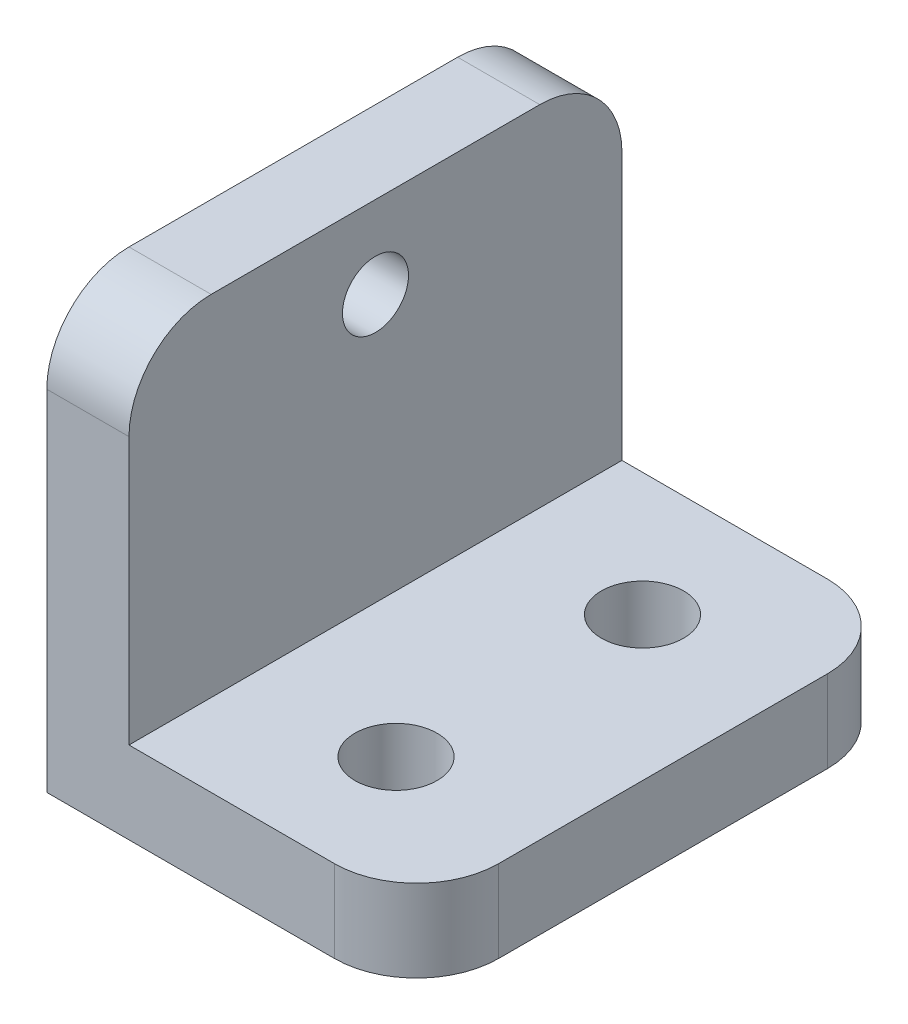
SolidWorks part; units mm, degrees
material "6061-T6 (SS)"
ref_plane "Front Plane" through (0, 0, 0) normal (0, 0, 1) x (1, 0, 0)
ref_plane "Top Plane" through (0, 0, 0) normal (0, 1, 0) x (1, 0, 0)
ref_plane "Right Plane" through (0, 0, 0) normal (1, 0, 0) x (0, 0, -1)
sketch "Sketch8" plane through (0, 0, 0) normal (0, 1, 0) x (1, 0, 0)
  line L0 (0, 19.05) -> (0, -19.05) construction
  line L1 (-14.2875, -19.05) -> (14.2875, -19.05)
  line L2 (-14.2875, -19.05) -> (-14.2875, 19.05)
  line L3 (-14.2875, 19.05) -> (14.2875, 19.05)
  line L4 (14.2875, -19.05) -> (14.2875, 19.05)
  line L5 (-14.2875, -19.05) -> (14.2875, 19.05) construction
  line L6 (-14.2875, 19.05) -> (14.2875, -19.05) construction
  line L7 (-7.9375, 19.05) -> (-7.9375, -19.05)
  point P0 (0, 0)
  dimension "D1" = 28.575
  dimension "D2" = 38.1
  dimension "D3" = 6.35
extrude "Boss-Extrude2" add sketch "Sketch8" along normal blind 6.35 contours L7 L3 L2 L1 | L3 L7 L1 L4 region at (-11.1125, 0, 0) region at (3.175, 0, 0)
extrude "Boss-Extrude3" add sketch "Sketch8<3>" along normal blind 26.9875 from surface contours L7 L3 L2 L1 region at (-11.1125, 0, 0) starting at face at (0, 6.35, 0)
sketch "Sketch8<3>" plane through (0, 0, 0) normal (0, 1, 0) x (1, 0, 0) same geometry as "Sketch8"
sketch "Sketch9" plane through (0, 0, 0) normal (0, 1, 0) x (1, 0, 0)
  line L1 (14.2875, 19.05) -> (-7.9375, 19.05) construction
  line L2 (14.2875, 19.05) -> (14.2875, -19.05) construction
  line L3 (14.2875, -19.05) -> (-7.9375, -19.05) construction
  line L4 (-7.9375, 19.05) -> (-7.9375, -19.05) construction
  line L6 (3.175, 19.05) -> (3.175, 0) construction
  line L7 (-7.9375, 0) -> (3.175, 0) construction
  line L8 (-7.9375, 0) -> (3.175, 19.05) construction
  line L9 (-7.9375, 19.05) -> (3.175, 0) construction
  line L10 (-14.2875, 19.05) -> (-7.9375, 0) construction
  line L11 (-7.9375, 19.05) -> (-14.2875, 0) construction
  line L12 (-7.9375, 19.05) -> (-7.9375, -19.05) construction
  point P4 (3.175, 9.525)
  point P5 (3.175, -9.525)
  point P10 (-2.3812, 9.525)
  point P14 (8.7313, 9.525)
  point P15 (8.7312, 0)
  point P16 (-2.3812, -9.525)
  point P17 (8.7313, -9.525)
  point P18 (-2.3812, 0)
  point P20 (-11.1125, 9.525)
  point P24 (-11.1125, -9.525)
hole_wizard "1/4 (0.25) Diameter Hole2" positions "Sketch10" profile "Sketch11" hole size "1/4" standard "ANSI Inch" end condition through all
sketch "Sketch10" plane through (0, 6.35, 0) normal (0, 1, 0) x (1, 0, 0)
  point P34 (3.175, -9.525)
  point P37 (3.175, 9.525)
sketch "Sketch11" plane through (3.175, 6.35, 9.525) normal (1, 0, 0) x (0, 0, 1)
  line L0 (0, 0) -> (0, 6.35)
  line L1 (0, 6.35) -> (3.175, 6.35)
  line L2 (3.175, 6.35) -> (3.175, 0)
  line L5 (3.175, 0) -> (0, 0)
  line L11 (0, -6.35) -> (0, 107.95) construction
  dimension "Thru Hole Dia." = 6.35
  dimension "Thru Hole Depth" = 6.35
sketch "Sketch12" plane through (0, 0, 0) normal (1, 0, 0) x (0, 0, -1)
  line L0 (-19.05, 33.3375) -> (19.05, 33.3375) construction
  circle A0 centre (0, 26.9875) radius 3.175
  dimension "D1" = 6.35
  dimension "D2" = 6.35
hole_wizard "1/4-20 Tapped Hole1" positions "Sketch13" profile "Sketch14" tap size "1/4-20" standard "ANSI Inch"
sketch "Sketch13" plane through (-7.9375, 0, 0) normal (1, 0, 0) x (0, 0, -1)
  point P0 (0, 26.9875)
sketch "Sketch14" plane through (-7.9375, 26.9875, 0) normal (0, 1, 0) x (0, 0, -1)
  line L0 (0, 0) -> (0, 18.0438)
  line L1 (0, 18.0438) -> (2.5527, 16.51)
  line L2 (2.5527, 16.51) -> (2.5527, 0)
  line L5 (2.5527, 0) -> (0, 0)
  line L10 (0, 18.0438) -> (-2.5527, 16.51) construction
  line L11 (0, -6.35) -> (0, 107.95) construction
  dimension "Tap Drill Dia." = 5.1054
  dimension "Tap Drill Depth" = 16.51
  dimension "Drill Angle" = 118
cosmetic thread "Hole Thread1" parameters "D1"=12.7, "D2"=6.35
fillet "Fillet1" radius 6.35 2 edges at (14.2875, 3.175, -19.05) (14.2875, 3.175, 19.05)
fillet "Fillet2" radius 6.35 2 edges at (-11.1125, 33.3375, -19.05) (-11.1125, 33.3375, 19.05)
